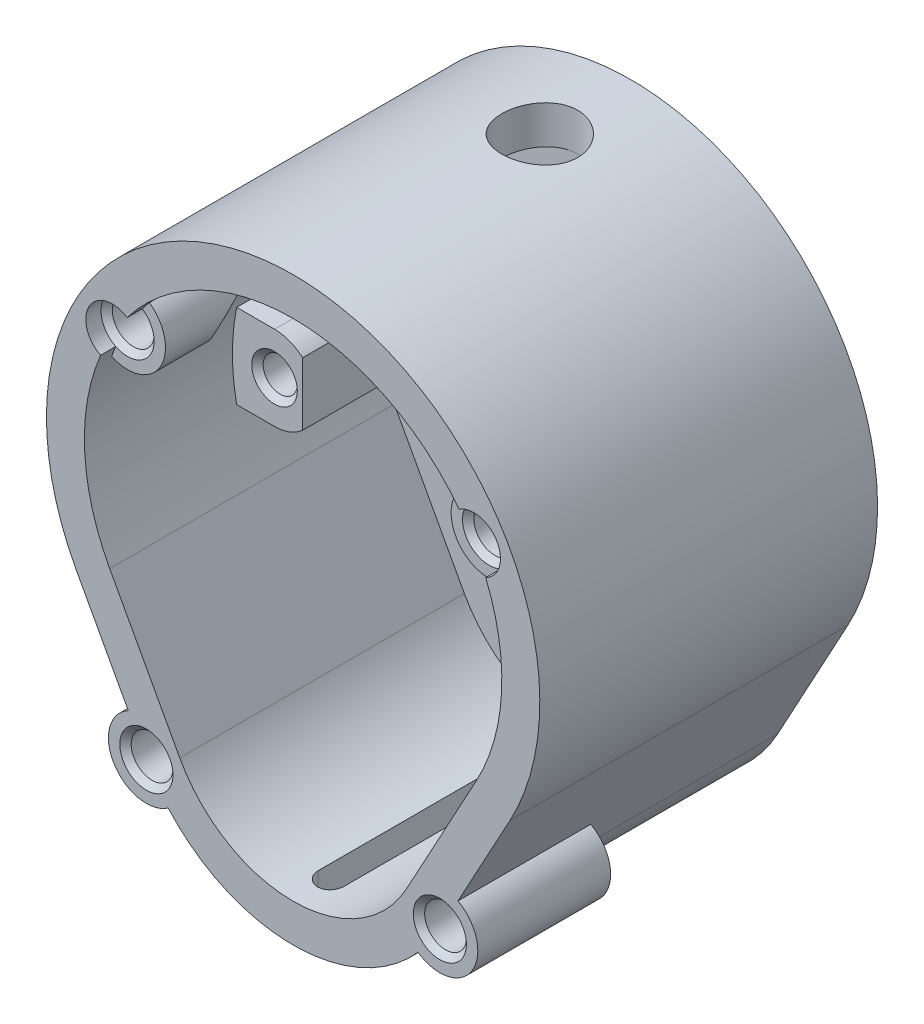
SolidWorks part; units mm, degrees
material "PET"
ref_plane "Front Plane" through (0, 0, 0) normal (0, 0, 1) x (1, 0, 0)
ref_plane "Top Plane" through (0, 0, 0) normal (0, 1, 0) x (1, 0, 0)
ref_plane "Right Plane" through (0, 0, 0) normal (1, 0, 0) x (0, 0, -1)
sketch "Sketch1" plane through (0, 0, 0) normal (0, 0, 1) x (1, 0, 0)
  line L0 (-28.5595, -15.5114) -> (-19.3326, -32.5)
  line L1 (28.5595, -15.5114) -> (19.3326, -32.5)
  line L2 (0, 0) -> (0, -22) construction
  arc A0 (28.5595, -15.5114) -> (-28.5595, -15.5114) centre (0, 0) ccw
  arc A1 (-19.3326, -32.5) -> (19.3326, -32.5) centre (0, -22) ccw
  dimension "D1" = 65
  dimension "D2" = 22
  dimension "D3" = 44
extrude "Boss-Extrude1" add sketch "Sketch1" along normal blind 7
sketch "Sketch2" plane through (0, 0, 7) normal (0, 0, 1) x (1, 0, 0)
  line L0 (0, 0) -> (0, -22) construction
  circle A0 centre (0, -22) radius 2.75
  dimension "D1" = 22
  dimension "D2" = 5.5
extrude "Cut-Extrude1" cut sketch "Sketch2" against normal through all
sketch "Sketch3" plane through (0, 0, 7) normal (0, 0, 1) x (1, 0, 0)
  circle A0 centre (0, -22) radius 7.1
  dimension "D1" = 14.2
extrude "Cut-Extrude2" cut sketch "Sketch3" against normal blind 5
sketch "Sketch4" plane through (0, 0, 7) normal (0, 0, 1) x (1, 0, 0)
  line L0 (-28.5595, -15.5114) -> (-19.3326, -32.5)
  line L1 (28.5595, -15.5114) -> (19.3326, -32.5)
  line L2 (-24.1658, -13.125) -> (-14.9388, -30.1136)
  line L3 (24.1658, -13.125) -> (14.9388, -30.1136)
  arc A0 (28.5595, -15.5114) -> (-28.5595, -15.5114) centre (0, 0) ccw
  arc A1 (-19.3326, -32.5) -> (19.3326, -32.5) centre (0, -22) ccw
  arc A2 (28.5595, -15.5114) -> (-28.5595, -15.5114) centre (0, 0) ccw construction
  arc A3 (-19.3326, -32.5) -> (19.3326, -32.5) centre (0, -22) ccw construction
  arc A4 (24.1658, -13.125) -> (-24.1658, -13.125) centre (0, 0) ccw
  arc A5 (-14.9388, -30.1136) -> (14.9388, -30.1136) centre (0, -22) ccw
  dimension "D1" = 5
extrude "Boss-Extrude2" add sketch "Sketch4" along normal blind 37.5
sketch "Sketch5" plane through (0, 0, 7) normal (0, 0, 1) x (1, 0, 0)
  line L0 (-21.95, 0) -> (21.95, 0) construction
  line L1 (-21.95, 5.55) -> (-26.9341, 5.55)
  line L2 (-21.95, -5.55) -> (-26.9341, -5.55)
  line L3 (21.95, 5.55) -> (26.9341, 5.55)
  line L4 (21.95, -5.55) -> (26.9341, -5.55)
  circle A0 centre (-21.95, 0) radius 2.25
  circle A1 centre (21.95, 0) radius 2.25
  arc A2 (-21.95, -5.55) -> (-21.95, 5.55) centre (-21.95, 0) ccw
  arc A3 (21.95, 5.55) -> (21.95, -5.55) centre (21.95, 0) ccw
  arc A4 (-26.9341, 5.55) -> (-26.9341, -5.55) centre (0, 0) ccw
  arc A5 (24.1658, -13.125) -> (-24.1658, -13.125) centre (0, 0) ccw construction
  arc A6 (26.9341, -5.55) -> (26.9341, 5.55) centre (0, 0) ccw
  dimension "D1" = 4.5
  dimension "D2" = 4.5
  dimension "D3" = 43.9
extrude "Boss-Extrude3" add sketch "Sketch5" along normal blind 18
sketch "Sketch6" plane through (0, 0, 7) normal (0, 0, 1) x (1, 0, 0)
  line L0 (-12, 15.95) -> (-12, -1.05) construction
  line L1 (-12, -1.05) -> (12, -1.05) construction
  line L2 (-12, 15.95) -> (12, 15.95) construction
  circle A0 centre (-12, 15.95) radius 1.7
  circle A1 centre (12, 15.95) radius 1.7
  circle A2 centre (-12, -1.05) radius 1.7
  circle A3 centre (12, -1.05) radius 1.7
  dimension "D1" = 3.4
  dimension "D2" = 3.4
  dimension "D3" = 3.4
  dimension "D4" = 3.4
  dimension "D6" = 15.95
  dimension "D5" = 12
  dimension "D7" = 24
  dimension "D8" = 24
  dimension "D9" = 17
extrude "Cut-Extrude3" cut sketch "Sketch6" against normal up to next
sketch "Sketch7" plane through (0, 0, 44.5) normal (0, 0, 1) x (1, 0, 0)
  line L1 (0, 0) -> (0, -44) construction
  line L2 (0, 0) -> (23.8157, 13.75) construction
  line L3 (0, 0) -> (-23.8157, 13.75) construction
  line L5 (0, 0) -> (-19.3326, -32.5) construction
  line L6 (0, 0) -> (19.3326, -32.5) construction
  circle A1 centre (-23.8157, 13.75) radius 5
  arc A2 (26.9341, 5.55) -> (-26.9341, 5.55) centre (0, 0) ccw construction
  circle A3 centre (23.8157, 13.75) radius 5
  arc A4 (24.1658, -13.125) -> (-24.1658, -13.125) centre (0, 0) ccw construction
  arc A6 (-19.3326, -32.5) -> (19.3326, -32.5) centre (0, -22) ccw construction
  arc A7 (28.5595, -15.5114) -> (-28.5595, -15.5114) centre (0, 0) ccw construction
  circle A10 centre (-19.3326, -32.5) radius 5
  circle A11 centre (19.3326, -32.5) radius 5
  dimension "D3" = 10
  dimension "D4" = 10
  dimension "D1" = 120
  dimension "D2" = 120
extrude "Boss-Extrude4" add sketch "Sketch7" against normal blind 17.5
sketch "Sketch9" plane through (0, 0, 0) normal (1, 0, 0) x (0, 0, -1)
  line L0 (-27, 27.5) -> (-35.6603, 22.5)
  line L1 (-35.6603, 22.5) -> (-27, 22.5)
  line L2 (-27, 22.5) -> (-27, 27.5)
  line L3 (0, 32.5) -> (-44.5, 32.5) construction
  line L4 (-44.5, 32.5) -> (-44.5, -15.5114) construction
  line L5 (0, 0) -> (-44.5, 0) construction
  dimension "D1" = 5
  dimension "D2" = 5
  dimension "D3" = 30
  dimension "D4" = 17.5
revolve "Cut-Revolve2" cut sketch "Sketch9" angle 145 mid plane about L5
sketch "Sketch10" plane through (0, 0, 44.5) normal (0, 0, 1) x (1, 0, 0)
  line L0 (-24.1658, -13.125) -> (-14.9388, -30.1136)
  line L1 (24.1658, -13.125) -> (14.9388, -30.1136)
  arc A0 (24.1658, -13.125) -> (-24.1658, -13.125) centre (0, 0) ccw
  arc A1 (-14.9388, -30.1136) -> (14.9388, -30.1136) centre (0, -22) ccw
extrude "Cut-Extrude4" cut sketch "Sketch10" against normal blind 2
sketch "Sketch11" plane through (0, 0, 44.5) normal (0, 0, 1) x (1, 0, 0)
  circle A0 centre (-23.8157, 13.75) radius 2.75
  arc A1 (-20.9324, 17.8349) -> (-25.9117, 9.2105) centre (0, 0) ccw construction
  circle A2 centre (23.8157, 13.75) radius 2.75
  arc A3 (25.9117, 9.2105) -> (20.9324, 17.8349) centre (0, 0) ccw construction
  circle A5 centre (-19.3326, -32.5) radius 2.75
  circle A6 centre (19.3326, -32.5) radius 2.75
  dimension "D1" = 5.5
  dimension "D2" = 5.5
  dimension "D3" = 5.5
  dimension "D4" = 5.5
extrude "Cut-Extrude6" cut sketch "Sketch11" against normal blind 12
sketch "Sketch12" plane through (0, 0, 0) normal (0, 0, -1) x (-1, 0, 0)
  line L0 (4.2, -33.55) -> (-5.3, -33.55) construction
  circle A0 centre (4.2, -33.55) radius 1.5
  circle A1 centre (0, -22) radius 2.75 construction
  circle A2 centre (-5.3, -33.55) radius 1.5
  dimension "D2" = 11.55
  dimension "D3" = 3
  dimension "D5" = 3
  dimension "D1" = 4.2
  dimension "D4" = 9.5
extrude "Cut-Extrude7" cut sketch "Sketch12" against normal up to next
chamfer "Chamfer1" distance 2 angle 45 4 edges at (13.7, 15.95, 7) (13.7, -1.05, 7) (-10.3, -1.05, 7) (-10.3, 15.95, 7)
sketch "Sketch13" plane through (0, 0, 25) normal (0, 0, 1) x (1, 0, 0)
  line L1 (18.25, -4.1367) -> (-18.25, -4.1367)
  line L2 (18.25, -4.1367) -> (18.25, 4.1367)
  line L3 (18.25, 4.1367) -> (-18.25, 4.1367)
  line L4 (-18.25, -4.1367) -> (-18.25, 4.1367)
  line L5 (18.25, -4.1367) -> (-18.25, 4.1367) construction
  line L6 (18.25, 4.1367) -> (-18.25, -4.1367) construction
  arc A1 (-21.95, -5.55) -> (-21.95, 5.55) centre (-21.95, 0) ccw construction
  point P0 (0, 0)
  dimension "D1" = 36.5
extrude "Cut-Extrude9" cut sketch "Sketch13" against normal up to surface (18 mm away) up to face at (15.7, 15.95, 7)
chamfer "Chamfer2" distance 0.75 angle 45 6 edges at (-5.7, -33.55, 0) (3.8, -33.55, 0) (24.2, 0, 25) (-19.7, 0, 25) (22.0826, -32.5, 44.5) (-16.5826, -32.5, 44.5)
sketch "Sketch14" plane through (0, 0, 44.5) normal (0, 0, 1) x (1, 0, 0)
  circle A0 centre (-23.8157, 13.75) radius 3.5
  circle A1 centre (23.8157, 13.75) radius 3.5
  dimension "D1" = 7
  dimension "D2" = 7
extrude "Cut-Extrude10" cut sketch "Sketch14" against normal up to surface (2 mm away) up to face at (-22.0195, 12.713, 42.5)
chamfer "Chamfer3" distance 0.75 angle 45 2 edges at (26.5657, 13.75, 42.5) (-21.0657, 13.75, 42.5)
sketch "Sketch15" plane through (0, 0, 0) normal (0, 1, 0) x (1, 0, 0)
  line L0 (0, -10) -> (0, -39.5) construction
  line L1 (1.75, -10) -> (1.75, -39.5)
  line L2 (-1.75, -10) -> (-1.75, -39.5)
  line L3 (-32.5, -44.5) -> (32.5, -44.5) construction
  line L4 (32.5, 0) -> (-32.5, 0) construction
  arc A0 (1.75, -10) -> (-1.75, -10) centre (0, -10) ccw
  arc A1 (-1.75, -39.5) -> (1.75, -39.5) centre (0, -39.5) ccw
  point P3 (0, -24.75)
  dimension "D1" = 1.75
  dimension "D2" = 5
  dimension "D3" = 10
extrude "Cut-Extrude11" cut sketch "Sketch15" against normal through all
sketch "Sketch16" plane through (0, 0, 0) normal (0, 1, 0) x (1, 0, 0)
  line L0 (0, 0) -> (0, -12) construction
  line L1 (-15.7, -7) -> (-8.3, -7) construction
  circle A0 centre (0, -12) radius 5
  dimension "D1" = 10
extrude "Cut-Extrude12" cut sketch "Sketch16" along normal through all
